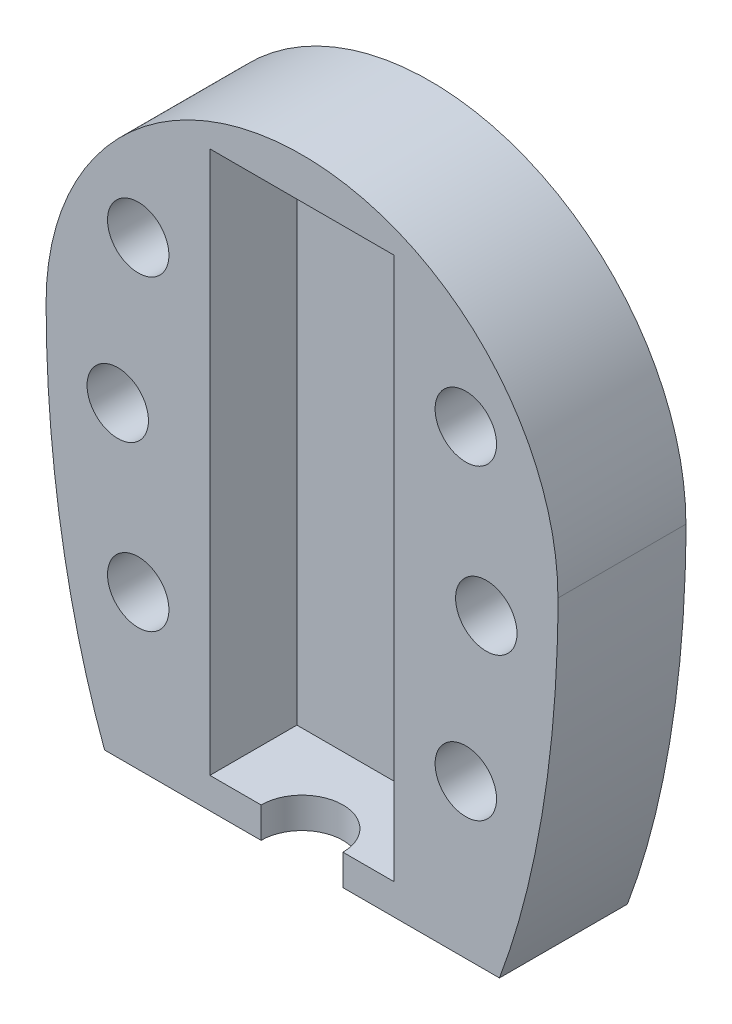
SolidWorks part; units mm, degrees
ref_plane "Alzado" through (0, 0, 0) normal (0, 0, 1) x (1, 0, 0)
ref_plane "Planta" through (0, 0, 0) normal (0, 1, 0) x (1, 0, 0)
ref_plane "Vista lateral" through (0, 0, 0) normal (1, 0, 0) x (0, 0, -1)
sketch "Croquis1" plane through (0, 0, 0) normal (0, 0, 1) x (1, 0, 0)
  line L3 (87.931, -29.1812) -> (116.4278, -29.1812)
  line L7 (88.1552, -30.3875) -> (116.6519, -30.3875)
  line L11 (-81.8244, -36.7669) -> (-52.4959, -36.7669)
  line L15 (-81.7478, -37.3531) -> (-52.4193, -37.3531)
  line L19 (-19.2847, -35) -> (19.2847, -35)
  line L31 (-19.2378, -40.0199) -> (19.3316, -40.0199)
  arc A0 (25, 0) -> (-25, 0) centre (0, 0) ccw
  arc A1 (119.1794, -11.1812) -> (85.1794, -11.1812) centre (102.1794, -11.1812) ccw
  arc A2 (-47.1602, -2.7669) -> (-87.1602, -2.7669) centre (-67.1602, -2.7669) ccw
  ellipse E0 centre (0, 0) end of major axis (0, -55) minor radius 25 (-25, 0) -> (-19.2847, -35) ccw
  ellipse E1 centre (102.1794, -11.1812) end of major axis (102.1794, 21.8188) minor radius 17 (119.1794, -11.1812) -> (116.4278, -29.1812) cw
  ellipse E2 centre (102.1794, -11.1812) end of major axis (102.1794, 21.8188) minor radius 17 (87.931, -29.1812) -> (85.1794, -11.1812) cw
  ellipse E3 centre (102.4035, -12.3875) end of major axis (102.4035, 20.6125) minor radius 17 (116.6519, -30.3875) -> (88.1552, -30.3875) cw
  ellipse E4 centre (-67.1602, -2.7669) end of major axis (-67.1602, -52.7669) minor radius 20 (-87.1602, -2.7669) -> (-81.8244, -36.7669) ccw
  ellipse E5 centre (-67.1602, -2.7669) end of major axis (-67.1602, -52.7669) minor radius 20 (-52.4959, -36.7669) -> (-47.1602, -2.7669) ccw
  ellipse E6 centre (-67.0836, -3.3531) end of major axis (-67.0836, -53.3531) minor radius 20 (-81.7478, -37.3531) -> (-52.4193, -37.3531) ccw
  ellipse E7 centre (0.0469, -5.0199) end of major axis (0.0469, -60.0199) minor radius 25 (-19.2378, -40.0199) -> (19.3316, -40.0199) ccw
  ellipse E8 centre (0, 0) end of major axis (0, -55) minor radius 25 (19.2847, -35) -> (25, 0) ccw
  point P21 (102.1794, 5.8188)
  point P28 (102.4035, -30.3875)
  point P38 (-67.1602, 17.2331)
  dimension "D1" = 25
  dimension "D4" = 17
  dimension "D2" = 28.4968
  dimension "D3" = 35
  dimension "D5" = 15
  dimension "D6" = 1.2064
  dimension "D7" = 54
extrude "Saliente-Extruir5" add sketch "Croquis1" along normal blind 12.5 contours A0 E0 L19 E8
sketch "Croquis10" plane through (0, 0, 12.5) normal (0, 0, 1) x (1, 0, 0)
  line L0 (-9, 21) -> (9, 21)
  line L1 (-9, 21) -> (-9, -32)
  line L2 (9, 21) -> (9, -32)
  line L3 (-9, -32) -> (9, -32)
  line L4 (-19.2847, -35) -> (19.2847, -35) construction
  dimension "D1" = 18
  dimension "D2" = 53
  dimension "D3" = 16
  dimension "D4" = 3
extrude "Cortar-Extruir1" cut sketch "Croquis10" against normal blind 8.5
sketch "Croquis11" plane through (0, -35, 0) normal (0, -1, 0) x (1, 0, 0)
  line L0 (-19.2847, 12.5) -> (19.2847, 12.5) construction
  circle A0 centre (0, 12.5) radius 4
  dimension "D1" = 8
extrude "Cortar-Extruir2" cut sketch "Croquis11" against normal blind 8
sketch "Croquis12" plane through (0, 0, 12.5) normal (0, 0, 1) x (1, 0, 0)
  line L0 (-19.2847, -35) -> (-4, -35) construction
  line L1 (-9, 21) -> (-9, -32) construction
  line L2 (4, -35) -> (19.2847, -35) construction
  line L3 (9, -32) -> (9, 21) construction
  circle A0 centre (16, -20) radius 3
  circle A1 centre (16, 10) radius 3
  circle A3 centre (-18, -5) radius 3
  circle A4 centre (18, -5) radius 3
  circle A5 centre (-16, -20) radius 3
  circle A6 centre (-16, 10) radius 3
  point P20 (0, 0)
  point P21 (0, 0)
  dimension "D2" = 15
  dimension "D18" = 6
  dimension "D3" = 30
  dimension "D4" = 45
  dimension "D5" = 7
  dimension "D6" = 9
  dimension "D8" = 15
  dimension "D9" = 30
  dimension "D10" = 45
  dimension "D11" = 7
  dimension "D12" = 9
extrude "Saliente-Extruir7" [suppressed] add sketch "Croquis12" along normal blind 8.5
extrude "Cortar-Extruir3" cut sketch "Croquis12<2>" against normal blind 8.7
sketch "Croquis12<2>" plane through (0, 0, 12.5) normal (0, 0, 1) x (1, 0, 0) same geometry as "Croquis12"
